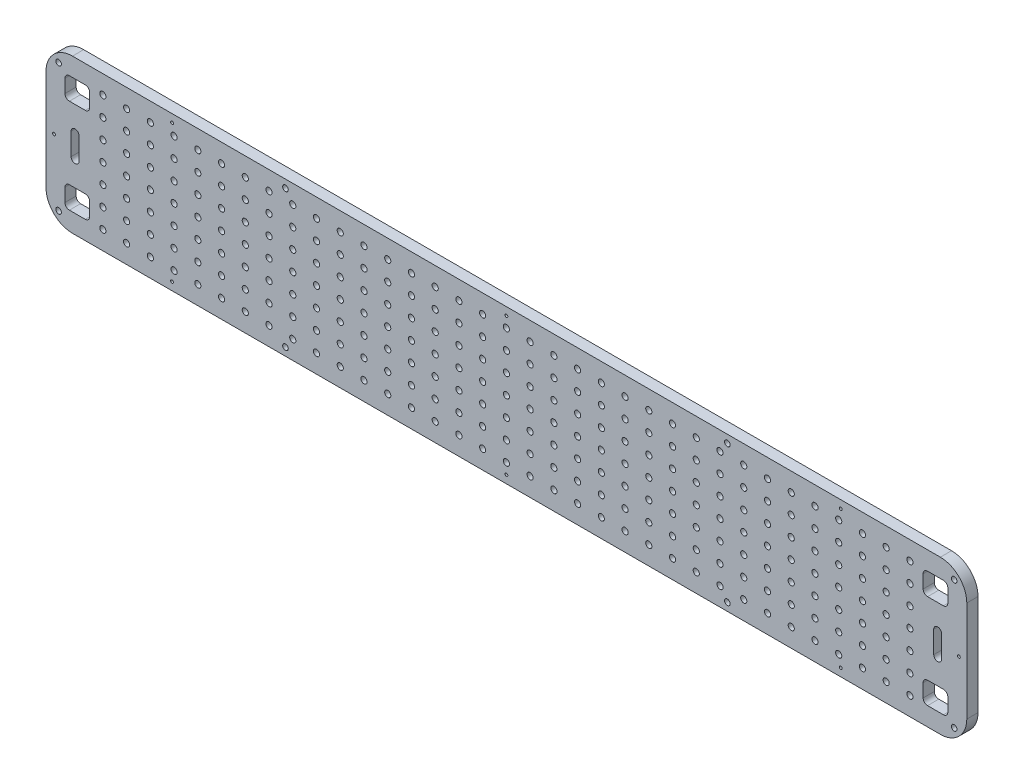
SolidWorks part; units mm, degrees
ref_plane "Front Plane" through (0, 0, 0) normal (0, 0, 1) x (1, 0, 0)
ref_plane "Top Plane" through (0, 0, 0) normal (0, 1, 0) x (1, 0, 0)
ref_plane "Right Plane" through (0, 0, 0) normal (1, 0, 0) x (0, 0, -1)
sketch "Sketch2" plane through (0, 0, 0) normal (0, 0, 1) x (1, 0, 0)
  circle A0 centre (0, 0) radius 5
  dimension "D1" = 10
sketch "Sketch1" plane through (0, 0, 0) normal (0, 0, 1) x (1, 0, 0)
  line L1 (-525, -90) -> (525, -90) construction
  line L2 (-525, -90) -> (-525, 90) construction
  line L3 (-525, 90) -> (525, 90) construction
  line L4 (525, -90) -> (525, 90) construction
  line L5 (-525, -90) -> (525, 90) construction
  line L6 (-525, 90) -> (525, -90) construction
  line L10 (-522, -87) -> (-522, 87)
  line L11 (-522, 87) -> (522, 87)
  line L12 (522, -87) -> (522, 87)
  line L13 (-522, -87) -> (522, -87)
  point P0 (0, 0)
  dimension "D1" = 3
  dimension "D2" = 180
  dimension "D3" = 1050
extrude "Boss-Extrude1" add sketch "Sketch1" along normal blind 12.7
fillet "Fillet1" radius 30 4 edges at (522, -87, 6.35) (522, 87, 6.35) (-522, -87, 6.35) (-522, 87, 6.35)
sketch "Sketch3" plane through (0, 0, 12.7) normal (0, 0, 1) x (1, 0, 0)
  circle A0 centre (-507.7279, 72.7279) radius 3.175
  circle A1 centre (-250.5, 78) radius 3.175
  circle A2 centre (250.5, 78) radius 3.175
  circle A3 centre (507.7279, 72.7279) radius 3.175
  circle A4 centre (507.7279, -72.7279) radius 3.175
  circle A5 centre (250.5, -78) radius 3.175
  circle A6 centre (-250.5, -78) radius 3.175
  circle A7 centre (-507.7279, -72.7279) radius 3.175
  circle A14 centre (-507.7279, 72.7279) radius 3.5 construction
  circle A17 centre (-507.7279, -72.7279) radius 3.5 construction
  circle A18 centre (-250.5, 78) radius 3.5 construction
  circle A19 centre (-250.5, -78) radius 3.5 construction
  circle A20 centre (250.5, 78) radius 3.5 construction
  circle A21 centre (250.5, -78) radius 3.5 construction
  circle A22 centre (507.7279, 72.7279) radius 3.5 construction
  circle A23 centre (507.7279, -72.7279) radius 3.5 construction
  dimension "D1" = 6.35
extrude "Cut-Extrude1" cut sketch "Sketch3" against normal through all
sketch "Sketch4" plane through (0, 0, 12.7) normal (0, 0, 1) x (1, 0, 0)
  line L1 (467.5, -54) -> (-467.5, -54)
  line L2 (467.5, -54) -> (467.5, -66)
  line L3 (467.5, -66) -> (-467.5, -66)
  line L4 (-467.5, -54) -> (-467.5, -66)
  line L5 (467.5, -54) -> (-467.5, -66) construction
  line L6 (467.5, -66) -> (-467.5, -54) construction
  line L7 (-467.5, 54) -> (467.5, 54)
  line L8 (-467.5, 54) -> (-467.5, 66)
  line L9 (-467.5, 66) -> (467.5, 66)
  line L10 (467.5, 54) -> (467.5, 66)
  line L11 (-467.5, 54) -> (467.5, 66) construction
  line L12 (-467.5, 66) -> (467.5, 54) construction
  line L20 (-492, -69) -> (492, -69)
  line L21 (-504, 57) -> (-504, -57)
  line L22 (492, 69) -> (-492, 69)
  line L23 (504, -57) -> (504, 57)
  arc A5 (-492, 69) -> (-504, 57) centre (-492, 57) ccw construction
  arc A6 (504, 57) -> (492, 69) centre (492, 57) ccw construction
  arc A7 (492, -69) -> (504, -57) centre (492, -57) ccw construction
  arc A8 (-504, -57) -> (-492, -69) centre (-492, -57) ccw construction
  arc A9 (-504, -57) -> (-492, -69) centre (-492, -57) ccw
  arc A10 (-492, 69) -> (-504, 57) centre (-492, 57) ccw
  arc A11 (504, 57) -> (492, 69) centre (492, 57) ccw
  arc A12 (492, -69) -> (504, -57) centre (492, -57) ccw
  point P6 (0, -60)
  point P13 (0, 60)
  point P20 (467.5, -60)
sketch "Sketch5" plane through (0, 0, 12.7) normal (0, 0, 1) x (1, 0, 0)
  line L0 (467.5, -66) -> (-467.5, -66) construction
  line L1 (-472.5, 66) -> (-500.5, 66)
  line L2 (-472.5, 66) -> (-472.5, 41)
  line L6 (-472.5, 41) -> (-500.5, 41)
  line L7 (-500.5, 66) -> (-500.5, 41)
  line L9 (-472.5, 66) -> (-500.5, 41) construction
  line L11 (-472.5, 41) -> (-500.5, 66) construction
  line L14 (-472.5, -66) -> (-500.5, -66)
  line L17 (-472.5, -66) -> (-472.5, -41)
  line L20 (-472.5, -41) -> (-500.5, -41)
  line L23 (-500.5, -66) -> (-500.5, -41)
  line L28 (-472.5, -66) -> (-500.5, -41) construction
  line L29 (-472.5, -41) -> (-500.5, -66) construction
  line L30 (472.5, 41) -> (500.5, 41)
  line L31 (472.5, 41) -> (472.5, 66)
  line L32 (472.5, 66) -> (500.5, 66)
  line L33 (500.5, 41) -> (500.5, 66)
  line L34 (472.5, 41) -> (500.5, 66) construction
  line L35 (472.5, 66) -> (500.5, 41) construction
  line L36 (472.5, -41) -> (500.5, -41)
  line L37 (472.5, -41) -> (472.5, -66)
  line L38 (472.5, -66) -> (500.5, -66)
  line L39 (500.5, -41) -> (500.5, -66)
  line L40 (472.5, -41) -> (500.5, -66) construction
  line L41 (472.5, -66) -> (500.5, -41) construction
  line L42 (-467.5, 66) -> (467.5, 66) construction
  line L43 (-467.5, -66) -> (-472.5, -66) construction
  line L44 (-472.5, 66) -> (-467.5, 66) construction
  line L45 (467.5, 66) -> (472.5, 66) construction
  line L46 (467.5, -66) -> (472.5, -66) construction
  point P5 (-486.5, 53.5)
  point P10 (-486.5, -53.5)
  point P15 (486.5, 53.5)
  point P20 (486.5, -53.5)
  dimension "D1" = 5
  dimension "D2" = 28
  dimension "D3" = 25
extrude "Cut-Extrude2" cut sketch "Sketch5" against normal through all both and the other way through all
fillet "Fillet2" radius 5 16 edges at (-500.5, 66, 6.35) (-472.5, 66, 6.35) (-472.5, 41, 6.35) (-500.5, 41, 6.35) (-500.5, -41, 6.35) (-472.5, -41, 6.35) (-500.5, -66, 6.35) (-472.5, -66, 6.35) (500.5, 66, 6.35) (472.5, 66, 6.35) (472.5, 41, 6.35) (500.5, 41, 6.35) (500.5, -66, 6.35) (472.5, -66, 6.35) (472.5, -41, 6.35) (500.5, -41, 6.35)
sketch "Sketch6" plane through (0, 0, 12.7) normal (0, 0, 1) x (1, 0, 0)
  line L0 (504, -57) -> (504, 57) construction
  line L1 (-489, -12.5) -> (-489, 12.5) construction
  line L2 (489, 0) -> (504, 0) construction
  line L3 (-489, 0) -> (-504, 0) construction
  line L4 (-504, 57) -> (-504, -57) construction
  line L5 (489, 12.5) -> (489, -12.5) construction
  line L6 (493.5, 12.5) -> (493.5, -12.5)
  line L7 (484.5, 12.5) -> (484.5, -12.5)
  line L8 (-493.5, -12.5) -> (-493.5, 12.5)
  line L9 (-484.5, -12.5) -> (-484.5, 12.5)
  circle A0 centre (489, 0) radius 4.5 construction
  circle A1 centre (-489, 0) radius 4.5 construction
  arc A2 (-493.5, -12.5) -> (-484.5, -12.5) centre (-489, -12.5) ccw
  arc A3 (493.5, 12.5) -> (484.5, 12.5) centre (489, 12.5) ccw
  arc A4 (484.5, -12.5) -> (493.5, -12.5) centre (489, -12.5) ccw
  arc A5 (-484.5, 12.5) -> (-493.5, 12.5) centre (-489, 12.5) ccw
  point P7 (504, 0)
  point P13 (489, 0)
  point P20 (-489, 0)
  dimension "D1" = 9
  dimension "D2" = 15
  dimension "D3" = 25
extrude "Cut-Extrude3" cut sketch "Sketch6" against normal through all both and the other way through all
sketch "Sketch7" plane through (0, 0, 12.7) normal (0, 0, 1) x (1, 0, 0)
  circle A0 centre (-513, 0) radius 1.625
  circle A2 centre (-379.114, -78) radius 1.625
  circle A3 centre (0, -78) radius 1.625
  circle A4 centre (379.114, -78) radius 1.625
  circle A5 centre (513, 0) radius 1.625
  circle A6 centre (379.114, 78) radius 1.625
  circle A7 centre (0, 78) radius 1.625
  circle A8 centre (-379.114, 78) radius 1.625
  circle A16 centre (-379.114, 78) radius 3.5 construction
  circle A17 centre (-513, 0) radius 3.5 construction
  circle A18 centre (-379.114, -78) radius 3.5 construction
  circle A19 centre (0, -78) radius 3.5 construction
  circle A20 centre (379.114, -78) radius 3.5 construction
  circle A21 centre (379.114, 78) radius 3.5 construction
  circle A22 centre (513, 0) radius 3.5 construction
  circle A24 centre (0, 78) radius 3.5 construction
  dimension "D1" = 3.25
extrude "Cut-Extrude4" cut sketch "Sketch7" against normal through all both and the other way through all
sketch "Sketch8" plane through (0, 0, 12.7) normal (0, 0, 1) x (1, 0, 0)
  line L0 (-467.5, 66) -> (-457.5, 66) construction
  line L1 (467.5, 66) -> (457.5, 66) construction
  circle A0 centre (-457.5, 66) radius 3.5
  dimension "D1" = 7
  dimension "D2" = 10
extrude "Cut-Extrude5" cut sketch "Sketch8" against normal through all both and the other way through all
pattern_linear "LPattern2" count 35 spacing 26.9118 along (1, 0, 0) of "Cut-Extrude5"
pattern_linear "LPattern3" count 7 spacing 22 along (0, -1, 0) of "LPattern2"
